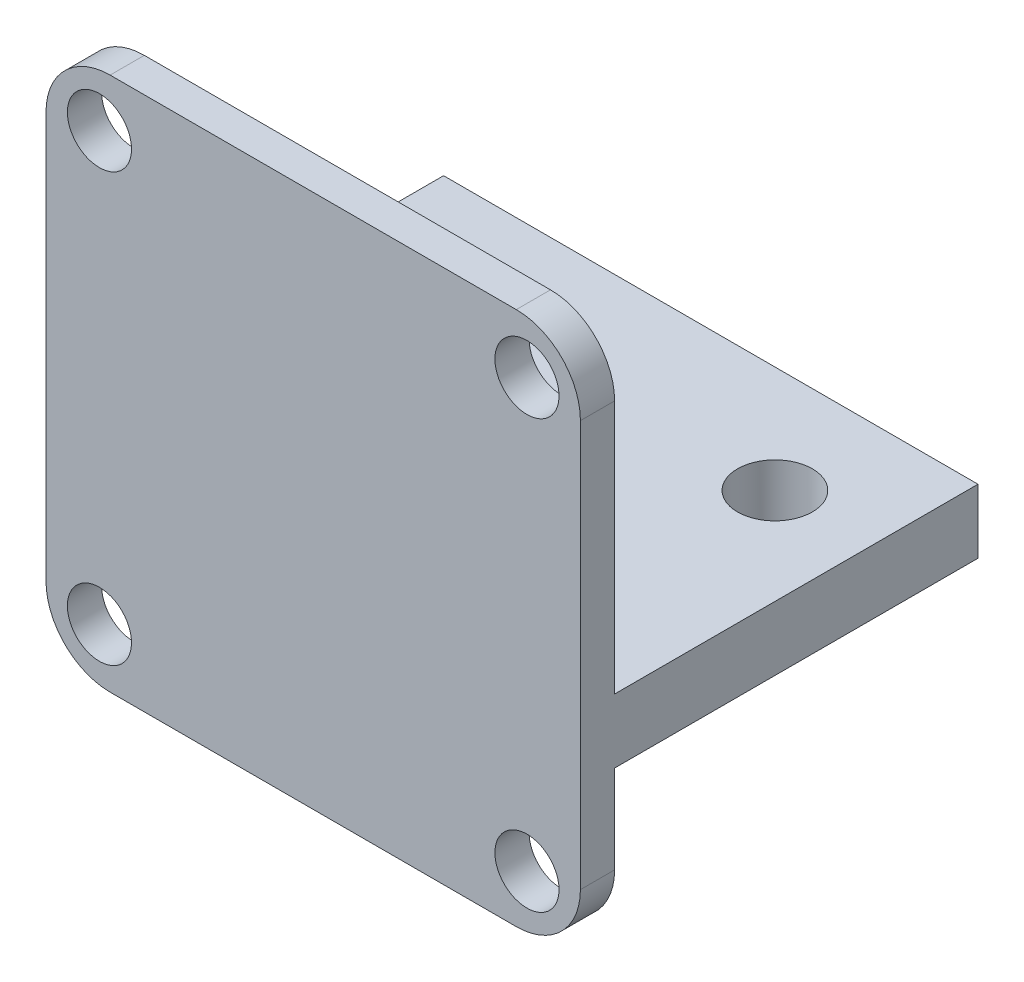
SolidWorks part; units mm, degrees
ref_plane "Front Plane" through (0, 0, 0) normal (0, 0, 1) x (1, 0, 0)
ref_plane "Top Plane" through (0, 0, 0) normal (0, 1, 0) x (1, 0, 0)
ref_plane "Right Plane" through (0, 0, 0) normal (1, 0, 0) x (0, 0, -1)
sketch "Sketch1" plane through (0, 0, 0) normal (0, 0, 1) x (1, 0, 0)
  line L1 (-9.5, -12.5) -> (9.5, -12.5)
  line L2 (-12.5, -9.5) -> (-12.5, 9.5)
  line L3 (-9.5, 12.5) -> (9.5, 12.5)
  line L4 (12.5, -9.5) -> (12.5, 9.5)
  line L5 (-12.5, -12.5) -> (12.5, 12.5) construction
  line L6 (-12.5, 12.5) -> (12.5, -12.5) construction
  line L7 (0, 12.5) -> (0, 0) construction
  line L8 (0, 0) -> (-12.5, 0) construction
  arc A0 (-9.5, -12.5) -> (-12.5, -9.5) centre (-9.5, -9.5) cw
  arc A1 (9.5, -12.5) -> (12.5, -9.5) centre (9.5, -9.5) ccw
  arc A2 (9.5, 12.5) -> (12.5, 9.5) centre (9.5, 9.5) cw
  arc A3 (-12.5, 9.5) -> (-9.5, 12.5) centre (-9.5, 9.5) cw
  circle A4 centre (-10, 10) radius 1.5
  circle A5 centre (10, 10) radius 1.5
  circle A6 centre (10, -10) radius 1.5
  circle A7 centre (-10, -10) radius 1.5
  point P0 (0, 0)
  dimension "D3" = 3
  dimension "D4" = 3
  dimension "D1" = 25
  dimension "D2" = 25
  dimension "D5" = 10
extrude "Boss-Extrude1" add sketch "Sketch1" along normal blind 1.6
sketch "Sketch2" plane through (0, 0, 0) normal (0, 0, -1) x (-1, 0, 0)
  line L0 (-12.5, 0) -> (12.5, 0) construction
  line L1 (-12.5, -9.5) -> (-12.5, 9.5) construction
  line L2 (12.5, 9.5) -> (12.5, -9.5) construction
  line L4 (-12.5, -5.375) -> (12.5, -5.375)
  line L5 (-12.5, -5.375) -> (-12.5, -2.375)
  line L6 (-12.5, -2.375) -> (12.5, -2.375)
  line L7 (12.5, -5.375) -> (12.5, -2.375)
  dimension "D1" = 2.375
  dimension "D2" = 3
extrude "Boss-Extrude2" add sketch "Sketch2" along normal blind 17
ref_plane "Plane1" through (0, 0, 0) normal (1, 0, 0) x (0, 0, -1)
sketch "Sketch3" plane through (0, -2.375, 0) normal (0, 1, 0) x (1, 0, 0)
  line L0 (0, 0) -> (0, 15.0798) construction
  line L1 (9.5, 0) -> (-9.5, 0) construction
  line L2 (0, -10.23) -> (0, 10.23) construction
  line L3 (-12.5, 0) -> (12.5, 0) construction
  circle A0 centre (-8, 12) radius 1.75
  circle A1 centre (8, 12) radius 1.75
  dimension "D1" = 3.5
  dimension "D2" = 8
  dimension "D3" = 12
extrude "Cut-Extrude1" cut sketch "Sketch3" against normal through all
